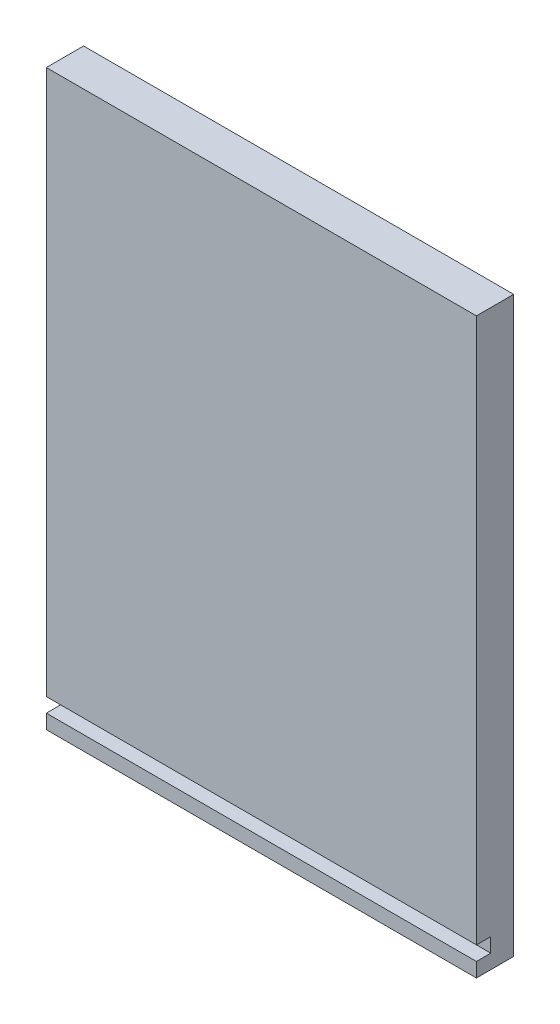
SolidWorks part; units mm, degrees
ref_plane "正面" through (0, 0, 0) normal (0, 0, 1) x (1, 0, 0)
ref_plane "平面" through (0, 0, 0) normal (0, 1, 0) x (1, 0, 0)
ref_plane "右側面" through (0, 0, 0) normal (1, 0, 0) x (0, 0, -1)
sketch "ｽｹｯﾁ1" plane through (0, 0, 0) normal (0, 0, 1) x (1, 0, 0)
  line L1 (-53.9801, 133.3357) -> (96.0199, 133.3357)
  line L2 (-53.9801, 133.3357) -> (-53.9801, -66.6643)
  line L3 (-53.9801, -66.6643) -> (96.0199, -66.6643)
  line L4 (96.0199, 133.3357) -> (96.0199, -66.6643)
  dimension "D3" = 200
  dimension "D4" = 150
extrude "ﾎﾞｽ - 押し出し1" add sketch "ｽｹｯﾁ1" along normal blind 13
sketch "ｽｹｯﾁ2" plane through (0, 0, 13) normal (0, 0, 1) x (1, 0, 0)
  line L1 (-53.9801, -56.6643) -> (96.0199, -56.6643)
  line L2 (-53.9801, -56.6643) -> (-53.9801, -61.6643)
  line L3 (-53.9801, -61.6643) -> (96.0199, -61.6643)
  line L4 (96.0199, -56.6643) -> (96.0199, -61.6643)
  line L5 (96.0199, -66.6643) -> (96.0199, 133.3357) construction
  line L7 (-53.9801, -66.6643) -> (96.0199, -66.6643) construction
  line L9 (-53.9801, 133.3357) -> (-53.9801, -66.6643) construction
  dimension "D1" = 5
  dimension "D2" = 150
  dimension "D3" = 5
extrude "ｶｯﾄ - 押し出し1" cut sketch "ｽｹｯﾁ2" against normal blind 5
